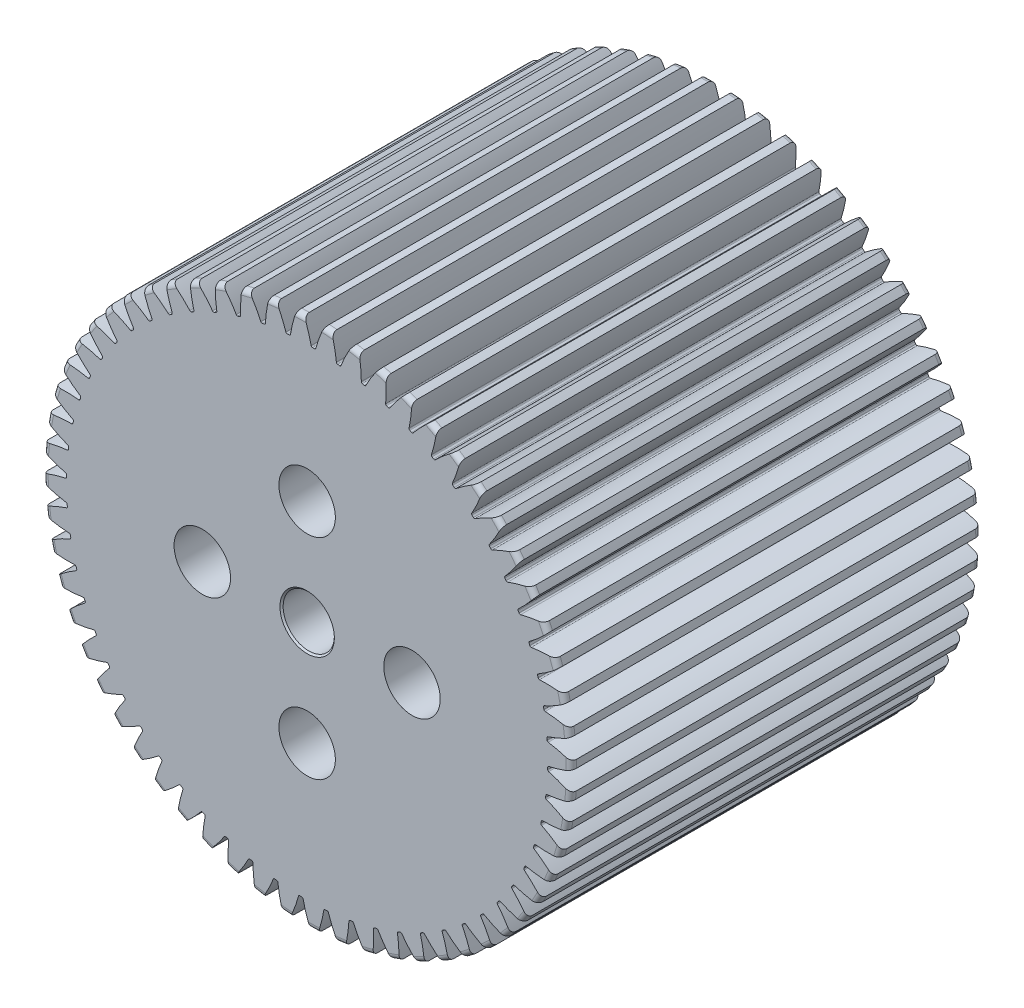
SolidWorks part; units mm, degrees
ref_plane "Front" through (0, 0, 0) normal (0, 0, 1) x (1, 0, 0)
ref_plane "Top" through (0, 0, 0) normal (0, 1, 0) x (1, 0, 0)
ref_plane "Right" through (0, 0, 0) normal (1, 0, 0) x (0, 0, -1)
sketch "Sketch1" plane through (0, 0, 0) normal (0, 0, 1) x (1, 0, 0)
  line L0 (-762, 0) -> (762, 0) construction
  circle A0 centre (0, 0) radius 32.766
  circle A1 centre (0, 0) radius 31.75 construction
  circle A3 centre (0, 0) radius 30.3847 construction
  dimension "D3" = 1.016
  dimension "D1" = 2.3813
extrude "Boss-Extrude1" add sketch "Sketch1" against normal blind 50.8
sketch "Sketch2" plane through (0, 0, 0) normal (1, 0, 0) x (0, 0, -1)
  line L1 (50.8, 0) -> (50.8, 4)
  point P1 (0, 0)
  point P6 (0, -32.766)
  point P7 (50.8, -32.766)
  point P9 (0, 32.766)
  point P11 (0, 0)
  point P14 (0, 0)
fillet "Fillet2" radius 0.6553 2 edges at (32.766, 0, -50.8) (32.766, 0, 0)
sketch "Sketch3" plane through (0, 0, 0) normal (0, 0, 1) x (1, 0, 0)
  line L0 (0, 0) -> (0, 32.766) construction
  line L1 (-10.2043, 28.036) -> (0, 31.75)
  line L2 (-9.5921, 31.75) -> (9.5921, 31.75) construction
  line L3 (-9.0136, 28.4693) -> (9.0136, 35.0307) construction
  line L4 (-10.2043, 28.036) -> (0, 0) construction
  line L5 (-24.5738, 16.9196) -> (0, 0) construction
  line L6 (-24.5738, 16.9196) -> (-7.961, 41.0478) construction
  line L7 (-7.0883, 28.981) -> (0, 0) construction
  line L8 (-7.0883, 28.981) -> (0.2955, 30.7869) construction
  arc A0 (-10.2043, 28.036) -> (-24.5738, 16.9196) centre (0, 0) ccw
  circle A1 centre (0, 0) radius 31.75 construction
  circle A2 centre (0, 0) radius 29.8352 construction
  arc A3 (-10.2043, 28.036) -> (-7.0883, 28.981) centre (0, 0) cw
  circle A4 centre (0, 0) radius 32.766 construction
  point P6 (0, 31.75)
  dimension "D1" = 10.8591
  dimension "D3" = 29.2943
  dimension "D5" = 7.6014
  dimension "D2" = 18.4605
  dimension "D4" = 3.2577
sketch "Sketch4" plane through (0, 0, 0) normal (0, 0, 1) x (1, 0, 0)
  line L0 (0, 0) -> (0.8308, 31.7282) construction
  line L2 (0, 31.75) -> (1.6617, 31.7065) construction
  line L4 (0.526, 29.8306) -> (0, 0) construction
  line L6 (-24.5738, 16.9196) -> (-7.961, 41.0478) construction
  line L7 (-24.5738, 16.9196) -> (-7.961, 41.0478) construction
  arc A0 (1.036, 29.8172) -> (0.526, 29.8306) centre (0, 0) ccw
  arc A1 (0, 31.75) -> (1.6617, 31.7065) centre (0, 0) cw construction
  circle A2 centre (0, 0) radius 31.75 construction
  circle A3 centre (0, 0) radius 29.8352 construction
  arc A5 (10.0983, 40.5749) -> (-7.961, 41.0478) centre (0, 0) ccw
  spline S0 degree 2 poles (-7.961, 41.0478) (-0.9392, 36.8055) (0.526, 29.8306) knots 0 0 0 1 1 1
  spline S1 degree 2 poles (10.0983, 40.5749) (2.8642, 36.7059) (1.036, 29.8172) knots 0 0 0 1 1 1
  dimension "D1" = 1.6624
extrude "Cut-Extrude1" cut sketch "Sketch4" against normal through all
fillet "Fillet1" radius 0.1662 2 edges at (1.036, 29.8172, -25.4) (0.526, 29.8306, -25.4)
pattern_circular "CirPattern1" count 60 over 360 about axis through (0, 0, -50.8) along (0, 0, 1) of "Cut-Extrude1", "Fillet1"
sketch "Sketch5" plane through (0, 0, 0) normal (0, 0, 1) x (1, 0, 0)
  line L0 (0, 4.3663) -> (0, 0) construction
  line L1 (-1.1906, 2.9433) -> (1.1906, 2.9433) construction
  line L2 (-1.1906, 2.9433) -> (-1.1906, 4.3663) construction
  line L3 (-1.1906, 4.3663) -> (1.1906, 4.3663) construction
  line L4 (1.1906, 2.9433) -> (1.1906, 4.3663) construction
  line L5 (-1.1906, 2.9433) -> (1.1906, 4.3663) construction
  line L6 (-1.1906, 4.3663) -> (1.1906, 2.9433) construction
  circle A0 centre (0, 0) radius 3.175
  point P3 (0, 3.6548)
  point P8 (0, 3.175)
  point P9 (0, -3.175)
  dimension "Bore Min" = 6.35
  dimension "Keyway Wd" = 2.3813
  dimension "Keyway Dpt." = 1.1913
extrude "Cut-Extrude2" cut sketch "Sketch5" against normal through all
chamfer "Chamfer1" distance 0.2 angle 45 1 edges at (3.175, 0, 0)
sketch "Pitch Dia" plane through (0, 0, 0) normal (0, 0, 1) x (1, 0, 0)
  circle A0 centre (0, 0) radius 31.75 construction
  circle A1 centre (0, 0) radius 31.75 construction
hole_wizard "M6 Clearance Hole1" positions "Sketch19" profile "Sketch20" hole size "M6" standard "ANSI Metric" end condition through all
sketch "Sketch19" plane through (0, 0, -50.8) normal (0, 0, 1) x (1, 0, 0)
  circle A0 centre (0, 0) radius 13
  point P0 (0, 13)
  point P2 (13, 0)
  point P4 (0, -13)
  point P6 (-13, 0)
  dimension "D1" = 26
sketch "Sketch20" plane through (0, 13, -50.8) normal (1, 0, 0) x (0, 1, 0)
  line L0 (0, 0) -> (0, 50.8441)
  line L1 (0, 50.8441) -> (3.5, 50.8441)
  line L2 (3.5, 50.8441) -> (3.5, 0)
  line L5 (3.5, 0) -> (0, 0)
  line L11 (0, -6.35) -> (0, 107.95) construction
  dimension "Thru Hole Dia." = 7
  dimension "Thru Hole Depth" = 50.8441
equation "\"D1@Boss-Extrude1\" = \"Face Wd@Sketch2\""
equation "\"D2@Sketch3\" = \"D1@Sketch3\"*1.7"
equation "\"D3@Sketch3\" = \"D1@Sketch3\"+\"D2@Sketch3\"-.001"
equation "\"D4@Sketch3\" = \"D1@Sketch3\"*.3"
equation "\"D5@Sketch3\" = \"D1@Sketch3\"-\"D4@Sketch3\""
equation "\"D1@Sketch4\" = 1.5708/(\"Number of Teeth@Sketch1\"/\"Ptich Dia@Sketch1\")"
equation "\"D1@Chamfer1\" = \"B Hub Dia@Sketch2\"*.025"
equation "\"D1@CirPattern1\" = \"Number of Teeth@Sketch1\""
equation "\"D1@Fillet1\" = \"D1@Sketch4\"*.1"
equation "\"D1@Fillet2\" = \"OD@Sketch1\"*.01"
equation "\"D1@Sketch1\" = 2.250/(\"Number of Teeth@Sketch1\"/\"Ptich Dia@Sketch1\")"
equation "\"D1@Sketch10\" = \"Set Screw Major Dia.@Sketch8\"*1.08"
equation "\"D2@Sketch11\" = \"D4@Helix/Spiral1\"*.125"
equation "\"D3@Sketch11\" = \"D4@Helix/Spiral1\"*.5"
equation "\"D1@Sketch12\" = \"Set Screw Major Dia.@Sketch8\""
equation "\"D1@Chamfer3\" = \"Set Screw Major Dia.@Sketch8\"*.08"
equation "\"D2@Sketch15\" = \"D4@Helix/Spiral1\"*.125"
equation "\"D3@Sketch15\" = \"D4@Helix/Spiral1\"*.5"
equation "\"D4@Helix/Spiral2\" = \"D4@Helix/Spiral1\""
equation "\"D3@Helix/Spiral1\" = \"D1@Sketch8\""
equation "\"D2@Sketch12\" = \"D2@Sketch8\""
equation "\"D3@Helix/Spiral2\" = \"D4@Helix/Spiral2\"+\"D2@Sketch12\""
